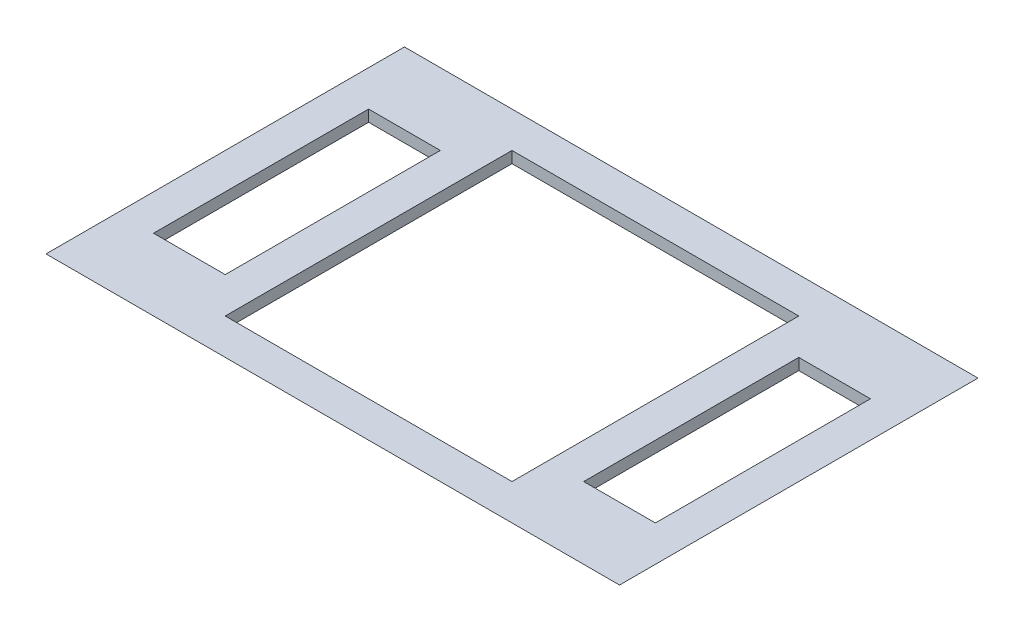
SolidWorks part; units mm, degrees
material "Teak"
ref_plane "Front Plane" through (0, 0, 0) normal (0, 0, 1) x (1, 0, 0)
ref_plane "Top Plane" through (0, 0, 0) normal (0, 1, 0) x (1, 0, 0)
ref_plane "Right Plane" through (0, 0, 0) normal (1, 0, 0) x (0, 0, -1)
sketch "Sketch1" plane through (0, 0, 0) normal (0, 1, 0) x (1, 0, 0)
  line L0 (0, 0) -> (0, 375)
  line L1 (0, 375) -> (225, 375)
  line L2 (225, 375) -> (225, 525)
  line L3 (225, 525) -> (375, 525)
  line L4 (375, 525) -> (375, 375)
  line L5 (375, 375) -> (600, 375)
  line L6 (600, 375) -> (600, 0)
  line L7 (600, 0) -> (0, 0)
  line L8 (225, 375) -> (375, 525) construction
  line L9 (150, 337.5) -> (450, 337.5)
  line L10 (150, 337.5) -> (150, 37.5)
  line L11 (150, 37.5) -> (450, 37.5)
  line L12 (450, 337.5) -> (450, 37.5)
  line L13 (37.5, 300) -> (112.5, 300)
  line L14 (37.5, 300) -> (37.5, 75)
  line L15 (37.5, 75) -> (112.5, 75)
  line L16 (112.5, 300) -> (112.5, 75)
  line L17 (487.5, 300) -> (562.5, 300)
  line L18 (487.5, 300) -> (487.5, 75)
  line L19 (487.5, 75) -> (562.5, 75)
  line L20 (562.5, 300) -> (562.5, 75)
  line L21 (225, 525) -> (375, 375) construction
  line L22 (375, 375) -> (225, 375)
  circle A0 centre (261.1091, 488.8909) radius 1.7
  circle A1 centre (300, 450) radius 55
  circle A2 centre (338.8909, 411.1091) radius 1.7
  circle A3 centre (338.8909, 488.8909) radius 1.7
  circle A4 centre (261.1091, 411.1091) radius 1.7
  point P5 (300, 525)
  point P10 (300, 0)
  point P23 (300, 337.5)
  point P24 (562.5, 187.5)
  point P25 (450, 187.5)
  point P26 (112.5, 187.5)
  point P27 (600, 187.5)
  point P30 (300, 450)
  dimension "D13" = 3.4
  dimension "D14" = 110
  dimension "D15" = 3.4
  dimension "D16" = 3.4
  dimension "D17" = 3.4
  dimension "D1" = 600
  dimension "D2" = 375
  dimension "D3" = 150
  dimension "D4" = 150
  dimension "D5" = 300
  dimension "D6" = 300
  dimension "D7" = 75
  dimension "D8" = 37.5
  dimension "D9" = 225
  dimension "D10" = 37.5
  dimension "D11" = 75
  dimension "D12" = 225
extrude "Boss-Extrude1" add sketch "Sketch1" along normal blind 12 contours L7 L6 L5 L4 L3 L2 L1 L0 A1 A0 L9 L12 L11 L10 L13 L16 L15 L14 L17 L20 L19 L18 region at (7.0755, 0, -187.5)
chamfer "Chamfer1" distance 12 angle 45 4 edges at (0, 0, -187.5) (300, 0, 0) (600, 0, -187.5) (300, 0, -375)
